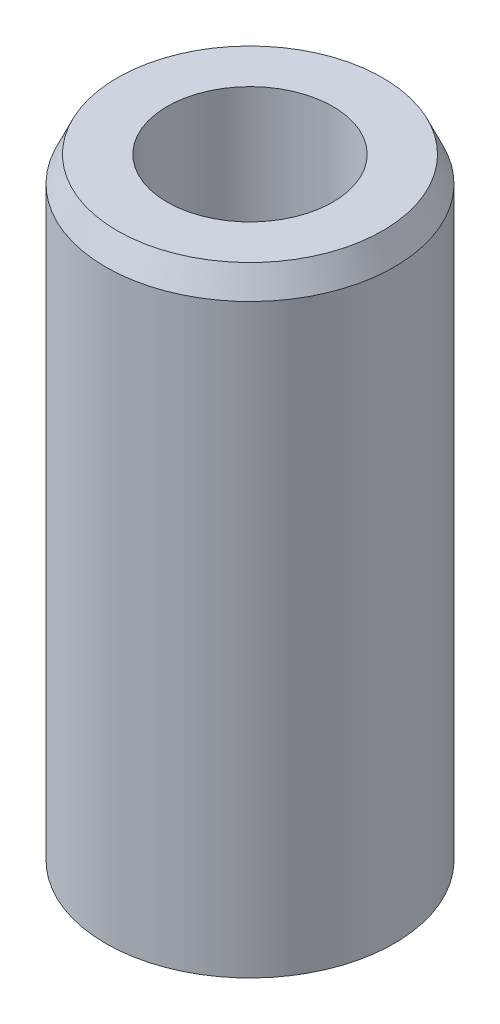
SolidWorks part; units mm, degrees
ref_plane "Front Plane" through (0, 0, 0) normal (0, 0, 1) x (1, 0, 0)
ref_plane "Top Plane" through (0, 0, 0) normal (0, 1, 0) x (1, 0, 0)
ref_plane "Right Plane" through (0, 0, 0) normal (1, 0, 0) x (0, 0, -1)
sketch "Sketch1" plane through (0, 0, 0) normal (0, 1, 0) x (1, 0, 0)
  circle A0 centre (0, 0) radius 15
  dimension "SHAFT_OD" = 30
extrude "Boss-Extrude1" add sketch "Sketch1" along normal blind 64.7808
sketch "Sketch2" plane through (0, 0, 0) normal (0, 1, 0) x (1, 0, 0)
  circle A0 centre (0, 0) radius 8.6187
  dimension "BORE_D" = 17.2374
extrude "Cut-Extrude1" cut sketch "Sketch2" along normal through all
chamfer "Chamfer1" distance 2.6556 angle 24.513 2 edges at (0, 64.7808, 15) (0, 0, 15) first distance on face at (0, 64.7808, 15) first distance on face at (0, 0, 8.6187)
